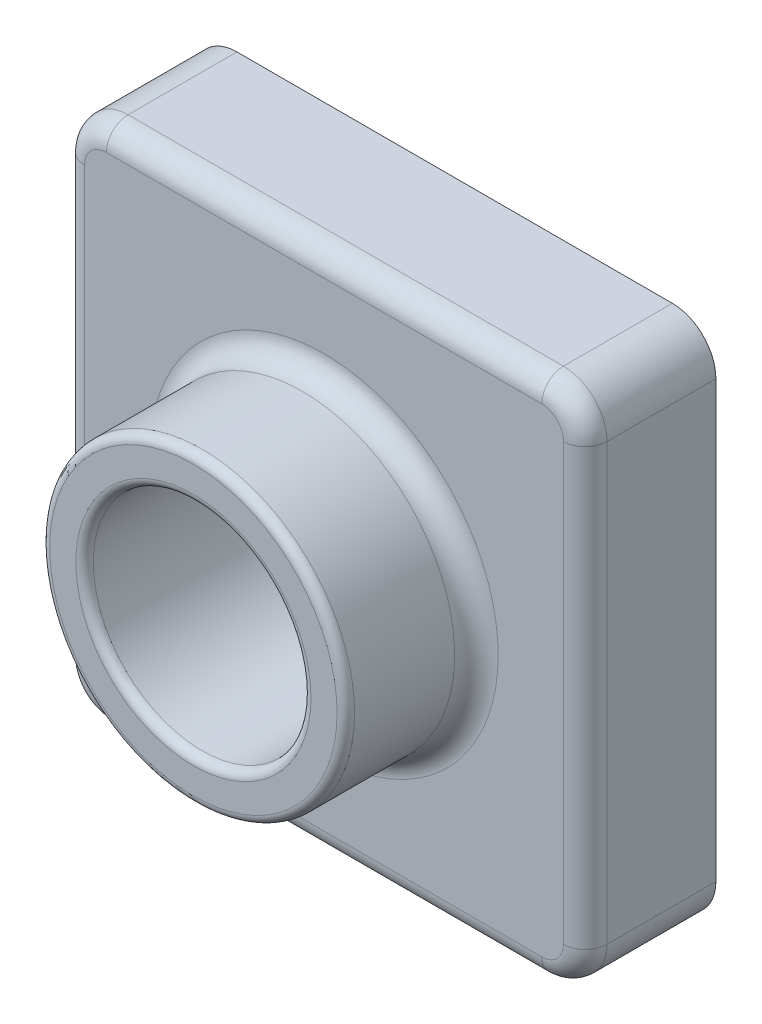
SolidWorks part; units mm, degrees
ref_plane "Front Plane" through (0, 0, 0) normal (0, 0, 1) x (1, 0, 0)
ref_plane "Top Plane" through (0, 0, 0) normal (0, 1, 0) x (1, 0, 0)
ref_plane "Right Plane" through (0, 0, 0) normal (1, 0, 0) x (0, 0, -1)
sketch "Croquis1" plane through (0, 0, 0) normal (0, 0, 1) x (1, 0, 0)
  line L1 (0, 0) -> (120, 0)
  line L2 (0, 0) -> (0, 120)
  line L3 (0, 120) -> (120, 120)
  line L4 (120, 0) -> (120, 120)
  dimension "D1" = 120
  dimension "D2" = 120
extrude "Saliente-Extruir1" add sketch "Croquis1" along normal blind 30
sketch "Croquis3" plane through (0, 0, 30) normal (0, 0, 1) x (1, 0, 0)
  line L0 (120, 120) -> (0, 120) construction
  line L1 (0, 120) -> (0, 0) construction
  circle A0 centre (60, 60) radius 35
  dimension "D3" = 70
  dimension "D1" = 60
  dimension "D2" = 60
extrude "Saliente-Extruir2" add sketch "Croquis3" along normal blind 30
sketch "Croquis4" plane through (0, 0, 60) normal (0, 0, 1) x (1, 0, 0)
  circle A0 centre (60, 60) radius 25
  circle A1 centre (60, 60) radius 35 construction
  dimension "D1" = 50
extrude "Cortar-Extruir1" cut sketch "Croquis4" against normal up to surface (60 mm away) up to face at (60, 60, 0)
fillet "Redondeo4" radius 2 2 edges at (95, 60, 60) (85, 60, 60)
fillet "Redondeo6" radius 10 4 edges at (120, 0, 15) (0, 0, 15) (0, 120, 15) (120, 120, 15)
fillet "Redondeo8" radius 5 9 edges at (25, 60, 30) (2.9289, 2.9289, 30) (0, 60, 30) (2.9289, 117.0711, 30) (60, 120, 30) (117.0711, 117.0711, 30) (120, 60, 30) (117.0711, 2.9289, 30) (60, 0, 30)
shell "Vaciado1" thickness 2
